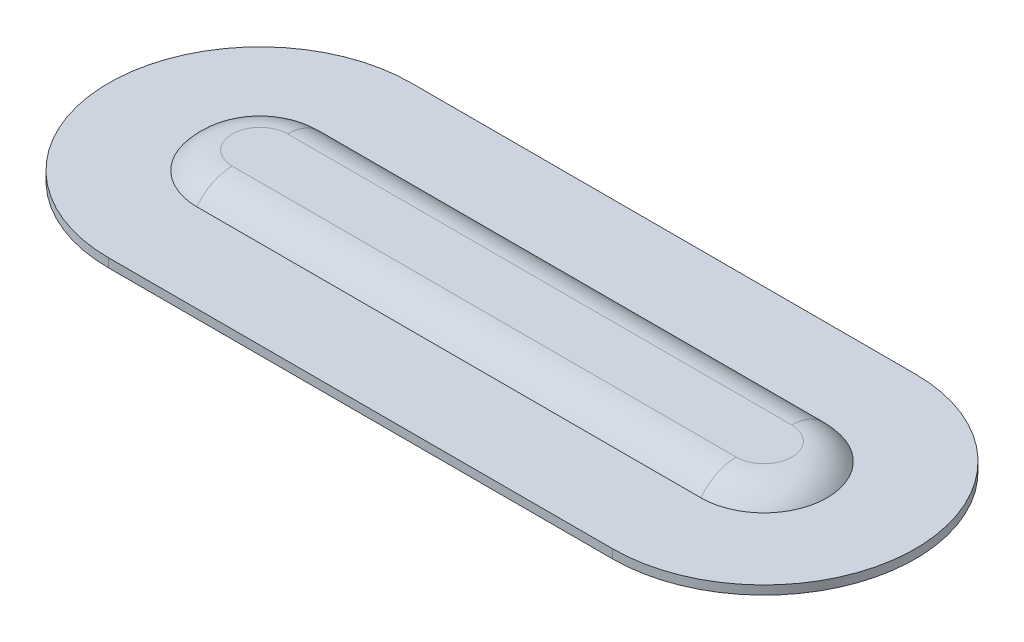
SolidWorks part; units mm, degrees
ref_plane "Front Plane" through (0, 0, 0) normal (0, 0, 1) x (1, 0, 0)
ref_plane "Top Plane" through (0, 0, 0) normal (0, 1, 0) x (1, 0, 0)
ref_plane "Right Plane" through (0, 0, 0) normal (1, 0, 0) x (0, 0, -1)
sketch "Sketch1" plane through (0, 0, 0) normal (0, 1, 0) x (1, 0, 0)
  line L0 (-28.5562, 0) -> (28.5562, 0) construction
  line L1 (-28.5562, 17.149) -> (28.5562, 17.149)
  line L2 (-28.5562, -17.149) -> (28.5563, -17.149)
  arc A0 (-28.5562, 17.149) -> (-28.5562, -17.149) centre (-28.5562, 0) ccw
  arc A1 (28.5563, -17.149) -> (28.5562, 17.149) centre (28.5562, 0) ccw
  point P2 (0, 0)
  dimension "D2" = 17.149
  dimension "D1" = 57.1125
  dimension "D3" = 57.1125
extrude "Boss-Extrude1" add sketch "Sketch1" along normal blind 1
sketch "Sketch2" plane through (0, 1, 0) normal (0, 1, 0) x (1, 0, 0)
  line L0 (-28.5563, -7.149) -> (28.5563, -7.149)
  line L1 (28.5563, 7.149) -> (-28.5563, 7.149)
  line L2 (28.5563, 0) -> (-28.5563, 0) construction
  arc A0 (-28.5563, 7.149) -> (-28.5563, -7.149) centre (-28.5563, 0) ccw
  arc A1 (28.5563, -7.149) -> (28.5563, 7.149) centre (28.5563, 0) ccw
  point P6 (0, 0)
  dimension "D1" = 7.149
  dimension "D2" = 7.149
  dimension "D3" = 14.298
  dimension "D4" = 57.1125
extrude "Boss-Extrude2" add sketch "Sketch2" along normal blind 2
fillet "Fillet1" radius 5 4 edges at (0, 3, -7.149) (0, 3, 7.149) (35.7052, 3, 0) (-35.7052, 3, 0)
